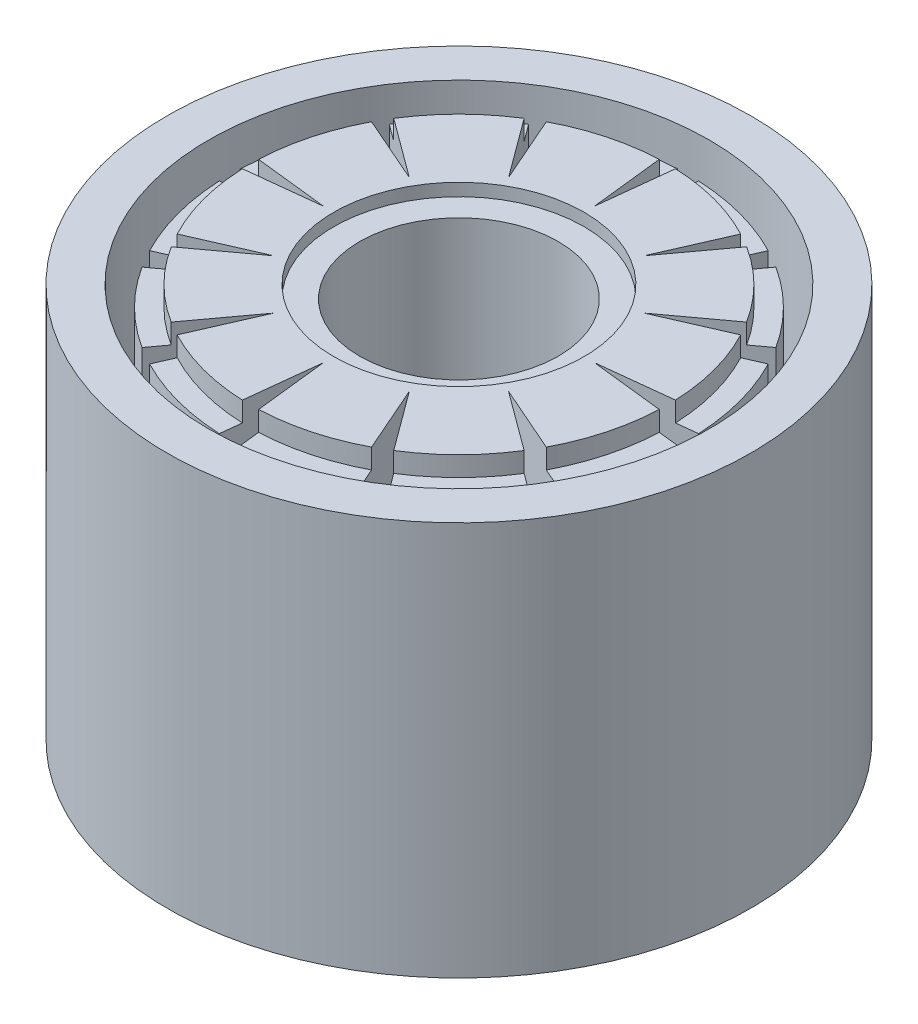
SolidWorks part; units mm, degrees
material "Cast Stainless Steel"
ref_plane "Front Plane" through (0, 0, 0) normal (0, 0, 1) x (1, 0, 0)
ref_plane "Top Plane" through (0, 0, 0) normal (0, 1, 0) x (1, 0, 0)
ref_plane "Right Plane" through (0, 0, 0) normal (1, 0, 0) x (0, 0, -1)
sketch "Sketch2" plane through (0, 0, 0) normal (0, 0, 1) x (1, 0, 0)
  line L0 (0, 0) -> (0, 21.3606) construction
  line L5 (4, 0) -> (12.5, 0)
  line L6 (12.5, 0) -> (14, 4)
  line L7 (14, 4) -> (14, 6)
  line L8 (14, 6) -> (6, 6)
  line L9 (6, 6) -> (6, 6.1)
  line L10 (6, 6.1) -> (11, 6.1)
  line L11 (11, 6.1) -> (11, 25)
  line L12 (11, 25) -> (4, 25)
  line L13 (4, 25) -> (4, 22)
  line L14 (4, 22) -> (3, 22)
  line L15 (3, 22) -> (3, 3)
  line L16 (3, 3) -> (4, 3)
  line L17 (4, 3) -> (4, 0)
  line L18 (14, 6) -> (14, 20.2979) construction
  line L19 (10, 25) -> (10, 24.05)
  line L20 (10, 24.05) -> (11, 24.05)
  line L21 (10, 6.1) -> (10, 7.05)
  line L22 (10, 7.05) -> (11, 7.05)
  point P23 (10, 23.1632)
  point P24 (11, 24.3282)
  dimension "D1" = 28
  dimension "D2" = 6
  dimension "D3" = 1.5
  dimension "D4" = 4
  dimension "D5" = 6
  dimension "D6" = 8
  dimension "D7" = 3
  dimension "D8" = 19
  dimension "D9" = 12
  dimension "D10" = 3
  dimension "D11" = 0.1
  dimension "D12" = 1
  dimension "D13" = 17
revolve "Revolve1" add sketch "Sketch2" angle 360 about L0 region at (7.4506, 11.822, 0)
sketch "Sketch3" plane through (0, 0, 0) normal (0, 0, 1) x (1, 0, 0)
  line L0 (-11, 6.1) -> (11, 6.1) construction
  line L1 (14, 6.1) -> (12, 6.1)
  line L2 (14, 6.1) -> (14, 25)
  line L3 (14, 25) -> (12, 25)
  line L4 (12, 6.1) -> (12, 25)
  line L5 (11, 25) -> (-11, 25) construction
  line L6 (14, 4) -> (14, 6) construction
  line L7 (0, 0) -> (0, 26.8317) construction
  dimension "D1" = 2
revolve "Revolve2" add sketch "Sketch3" angle 360 about L7
sketch "Sketch4" plane through (0, 0, 0) normal (0, -1, 0) x (1, 0, 0)
  line L0 (0, 9.5) -> (0, -9.5) construction
  line L1 (-8, 0) -> (8, 0) construction
  circle A0 centre (-8, 0) radius 1.25
  circle A1 centre (0, 9.5) radius 1.25
  circle A2 centre (8, 0) radius 1.25
  circle A3 centre (0, -9.5) radius 1.25
  dimension "D3" = 2.5
  dimension "D1" = 16
  dimension "D2" = 19
extrude "Cut-Extrude1" cut sketch "Sketch4" against normal up to next (6 mm away)
sketch "Sketch5" plane through (0, 25, 0) normal (0, 1, 0) x (1, 0, 0)
  line L2 (0, 6.5) -> (-0.5, 10.9886)
  line L3 (0, 6.5) -> (0.5, 10.9886)
  circle A0 centre (0, 0) radius 6 construction
  circle A1 centre (0, 0) radius 6 construction
  circle A3 centre (0, 0) radius 11 construction
  arc A6 (-0.5, 10.9886) -> (0.5, 10.9886) centre (0, 0) cw
  circle A7 centre (0, 0) radius 6.5 construction
  circle A9 centre (0, 0) radius 11 construction
  point P10 (0, 6.5)
  point P11 (0.5, 12.1496)
  point P13 (0, 11)
  dimension "D1" = 1
  dimension "D2" = 0.5
extrude "Cut-Extrude2" cut sketch "Sketch5" against normal up to surface (18.9 mm away) up to face at (0, 6.1, -10)
pattern_circular "CirPattern1" count 12 over 360 about axis through (0, 25, 0) along (0, -1, 0) of "Cut-Extrude2"
sketch "Sketch6" plane through (0, 25, 0) normal (0, 1, 0) x (1, 0, 0)
  circle A0 centre (0, 0) radius 6
  circle A1 centre (0, 0) radius 4.5
  dimension "D1" = 12
  dimension "D2" = 9
extrude "Cut-Extrude3" cut sketch "Sketch6" against normal blind 0.6
sketch "Sketch7" plane through (0, 0, 0) normal (1, 0, 0) x (0, 0, -1)
  line L0 (0, 0) -> (0, 5)
  line L2 (-6, 6.1) -> (6, 6.1) construction
  line L3 (-6, 6.1) -> (6, 6.1) construction
  line L4 (0, 0) -> (14, 0)
  line L5 (14, 0) -> (14, 6.1)
  line L6 (14, 4) -> (14, 6) construction
  line L7 (0, 5) -> (6, 5)
  line L8 (6, 5) -> (6, 6.1)
  line L9 (6, 6.1) -> (14, 6.1)
  line L10 (4.6593, 25) -> (0.389, 25) construction
  dimension "D1" = 20
revolve "Cut-Revolve1" cut sketch "Sketch7" angle 360 about L0
sketch "Sketch8" plane through (0, 5, 0) normal (0, -1, 0) x (1, 0, 0)
  circle A0 centre (0, 0) radius 4.7625
  dimension "D1" = 9.525
extrude "Cut-Extrude4" cut sketch "Sketch8" against normal through all
equation "\"D1@Sketch8\"=.375in"
